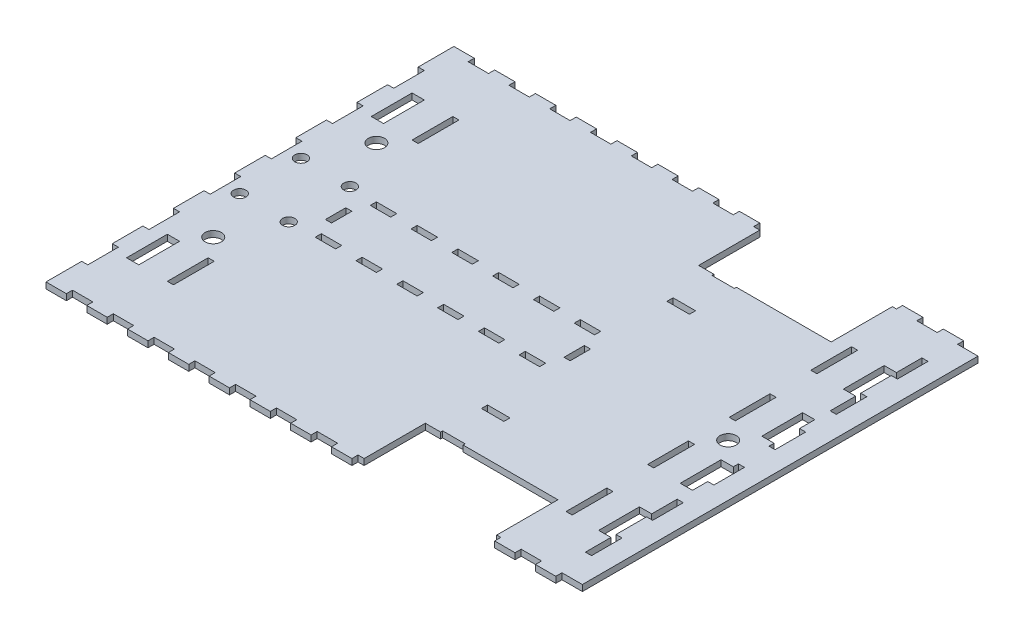
SolidWorks part; units mm, degrees
ref_plane "Front Plane" through (0, 0, 0) normal (0, 0, 1) x (1, 0, 0)
ref_plane "Top Plane" through (0, 0, 0) normal (0, 1, 0) x (1, 0, 0)
ref_plane "Right Plane" through (0, 0, 0) normal (1, 0, 0) x (0, 0, -1)
sketch "Sketch3" plane through (0, 0, 0) normal (0, 1, 0) x (1, 0, 0)
  line L0 (0, 0) -> (-300, 0) construction
  line L1 (-300, -97) -> (-300, 97)
  line L2 (-290, 100) -> (-300, 100)
  line L3 (-290, 97) -> (-290, 100)
  line L4 (-280, 97) -> (-290, 97)
  line L5 (-300, 100) -> (-300, 97)
  line L6 (-270, 100) -> (-280, 100)
  line L7 (-270, 97) -> (-270, 100)
  line L8 (-260, 97) -> (-270, 97)
  line L9 (-280, 100) -> (-280, 97)
  line L10 (-250, 100) -> (-260, 100)
  line L11 (-250, 97) -> (-250, 100)
  line L12 (-240, 97) -> (-250, 97)
  line L13 (-260, 100) -> (-260, 97)
  line L14 (-150, -100) -> (-150, 100) construction
  line L15 (-230, 100) -> (-240, 100)
  line L16 (-230, 97) -> (-230, 100)
  line L17 (-220, 97) -> (-230, 97)
  line L18 (-240, 100) -> (-240, 97)
  line L19 (-210, 100) -> (-220, 100)
  line L20 (-210, 97) -> (-210, 100)
  line L21 (-200, 97) -> (-210, 97)
  line L22 (-40, 97) -> (-40, -97)
  line L23 (-50, 37.5) -> (-53, 37.5)
  line L24 (-50, 7.5) -> (-53, 7.5)
  line L25 (-50, -45.947) -> (-50, 45.947) construction
  line L26 (-247, 37.5) -> (-250, 37.5) construction
  line L27 (-247, 7.5) -> (-250, 7.5) construction
  line L28 (-247, 48.5) -> (-247, -48.5) construction
  line L29 (-247, 48.5) -> (-223, 48.5) construction
  line L30 (-223, 48.5) -> (-223, -48.5) construction
  line L31 (-210, 15) -> (-90, 15) construction
  line L32 (-90, 15) -> (-90, 5) construction
  line L33 (-50, 7.5) -> (-50, 22.5)
  line L34 (-220, 100) -> (-220, 97)
  line L35 (-190, 100) -> (-200, 100)
  line L36 (-190, 97) -> (-190, 100)
  line L37 (-180, 97) -> (-190, 97)
  line L38 (-200, 100) -> (-200, 97)
  line L39 (-170, 100) -> (-180, 100)
  line L40 (-170, 97) -> (-170, 100)
  line L41 (-160, 97) -> (-170, 97)
  line L42 (-180, 100) -> (-180, 97)
  line L43 (-150, 100) -> (-160, 100)
  line L44 (-150, 97) -> (-150, 100)
  line L45 (-140, 97) -> (-150, 97)
  line L46 (-160, 100) -> (-160, 97)
  line L47 (-130, 100) -> (-140, 100)
  line L48 (-130, 97) -> (-130, 100)
  line L49 (-120, 97) -> (-130, 97)
  line L50 (-140, 100) -> (-140, 97)
  line L51 (-110, 100) -> (-120, 100)
  line L52 (-110, 97) -> (-110, 100)
  line L53 (-100, 97) -> (-110, 97)
  line L54 (-120, 100) -> (-120, 97)
  line L55 (-90, 100) -> (-100, 100)
  line L56 (-90, 97) -> (-90, 100)
  line L57 (-80, 97) -> (-90, 97)
  line L58 (-100, 100) -> (-100, 97)
  line L59 (-70, 100) -> (-80, 100)
  line L60 (-70, 97) -> (-70, 100)
  line L61 (-60, 97) -> (-70, 97)
  line L62 (-80, 100) -> (-80, 97)
  line L63 (-50, 100) -> (-60, 100)
  line L64 (-50, 97) -> (-50, 100)
  line L65 (-40, 97) -> (-50, 97)
  line L66 (-60, 100) -> (-60, 97)
  line L67 (-50, 22.5) -> (-53, 22.5)
  line L68 (-210, -15) -> (-90, -15) construction
  line L69 (-53, 7.5) -> (-53, 22.5)
  line L70 (-50, 37.5) -> (-50, 52.5)
  line L71 (-50, 52.5) -> (-53, 52.5)
  line L72 (-53, 37.5) -> (-53, 52.5)
  line L73 (-50, 67.5) -> (-53, 67.5)
  line L74 (-50, 67.5) -> (-50, 82.5)
  line L75 (-50, 82.5) -> (-53, 82.5)
  line L76 (-60, -100) -> (-60, -97)
  line L77 (-40, -97) -> (-50, -97)
  line L78 (-50, -97) -> (-50, -100)
  line L79 (-50, -100) -> (-60, -100)
  line L80 (-80, -100) -> (-80, -97)
  line L81 (-60, -97) -> (-70, -97)
  line L82 (-70, -97) -> (-70, -100)
  line L83 (-70, -100) -> (-80, -100)
  line L84 (-100, -100) -> (-100, -97)
  line L85 (-80, -97) -> (-90, -97)
  line L86 (-90, -97) -> (-90, -100)
  line L87 (-90, -100) -> (-100, -100)
  line L88 (-120, -100) -> (-120, -97)
  line L89 (-100, -97) -> (-110, -97)
  line L90 (-110, -97) -> (-110, -100)
  line L91 (-110, -100) -> (-120, -100)
  line L92 (-140, -100) -> (-140, -97)
  line L93 (-120, -97) -> (-130, -97)
  line L94 (-130, -97) -> (-130, -100)
  line L95 (-130, -100) -> (-140, -100)
  line L96 (-160, -100) -> (-160, -97)
  line L97 (-140, -97) -> (-150, -97)
  line L98 (-150, -97) -> (-150, -100)
  line L99 (-150, -100) -> (-160, -100)
  line L100 (-180, -100) -> (-180, -97)
  line L101 (-160, -97) -> (-170, -97)
  line L102 (-170, -97) -> (-170, -100)
  line L103 (-170, -100) -> (-180, -100)
  line L104 (-200, -100) -> (-200, -97)
  line L105 (-180, -97) -> (-190, -97)
  line L106 (-190, -97) -> (-190, -100)
  line L107 (-190, -100) -> (-200, -100)
  line L108 (-247, -48.5) -> (-223, -48.5) construction
  line L109 (-247, 7.5) -> (-247, 22.5) construction
  line L110 (-220, -100) -> (-220, -97)
  line L111 (-53, 67.5) -> (-53, 82.5)
  line L112 (-53, -67.5) -> (-53, -82.5)
  line L113 (-50, -82.5) -> (-53, -82.5)
  line L114 (-200, -97) -> (-210, -97)
  line L115 (-210, -97) -> (-210, -100)
  line L116 (-210, -100) -> (-220, -100)
  line L117 (-240, -100) -> (-240, -97)
  line L118 (-220, -97) -> (-230, -97)
  line L119 (-230, -97) -> (-230, -100)
  line L120 (-230, -100) -> (-240, -100)
  line L121 (-50, -67.5) -> (-50, -82.5)
  line L122 (-260, -100) -> (-260, -97)
  line L123 (-240, -97) -> (-250, -97)
  line L124 (-250, -97) -> (-250, -100)
  line L125 (-250, -100) -> (-260, -100)
  line L126 (-280, -100) -> (-280, -97)
  line L127 (-260, -97) -> (-270, -97)
  line L128 (-270, -97) -> (-270, -100)
  line L129 (-270, -100) -> (-280, -100)
  line L130 (-300, -100) -> (-300, -97)
  line L131 (-210, 15) -> (-210, -15) construction
  line L132 (-253, -15) -> (-243, -15)
  line L133 (-233, -15) -> (-223, -15)
  line L188 (-247, 22.5) -> (-250, 22.5) construction
  line L189 (-250, 7.5) -> (-250, 22.5) construction
  line L190 (-247, 37.5) -> (-247, 52.5) construction
  line L191 (-247, 52.5) -> (-250, 52.5) construction
  line L192 (-250, 37.5) -> (-250, 52.5) construction
  line L193 (-247, 67.5) -> (-250, 67.5) construction
  line L194 (-247, 67.5) -> (-247, 82.5) construction
  line L195 (-247, 82.5) -> (-250, 82.5) construction
  line L196 (-250, 67.5) -> (-250, 82.5) construction
  line L197 (-250, -67.5) -> (-250, -82.5) construction
  line L198 (-247, -82.5) -> (-250, -82.5) construction
  line L199 (-247, -67.5) -> (-247, -82.5) construction
  line L200 (-247, -67.5) -> (-250, -67.5) construction
  line L201 (-250, -37.5) -> (-250, -52.5) construction
  line L202 (-247, -52.5) -> (-250, -52.5) construction
  line L203 (-247, -37.5) -> (-247, -52.5) construction
  line L204 (-250, -7.5) -> (-250, -22.5) construction
  line L205 (-247, -22.5) -> (-250, -22.5) construction
  line L206 (-247, -7.5) -> (-247, -22.5) construction
  line L207 (-247, -7.5) -> (-250, -7.5) construction
  line L208 (-247, -37.5) -> (-250, -37.5) construction
  line L209 (-50, -67.5) -> (-53, -67.5)
  line L210 (-53, -37.5) -> (-53, -52.5)
  line L211 (-50, -52.5) -> (-53, -52.5)
  line L212 (-50, -37.5) -> (-50, -52.5)
  line L213 (-53, -7.5) -> (-53, -22.5)
  line L214 (-50, -22.5) -> (-53, -22.5)
  line L215 (-50, -7.5) -> (-50, -22.5)
  line L216 (-50, -7.5) -> (-53, -7.5)
  line L217 (-50, -37.5) -> (-53, -37.5)
  line L218 (-210, 0) -> (-258, 0)
  line L219 (-258, -5) -> (-255, -5)
  line L220 (-163, 15) -> (-173, 15)
  line L221 (-243, -12) -> (-243, -15)
  line L222 (-143, 15) -> (-143, 12)
  line L223 (-173, -15) -> (-173, -12)
  line L224 (-163, -15) -> (-173, -15)
  line L225 (-183, 12) -> (-183, 15)
  line L226 (-153, 15) -> (-153, 12)
  line L227 (-163, -12) -> (-163, -15)
  line L228 (-243, -12) -> (-253, -12)
  line L229 (-193, -15) -> (-193, -12)
  line L230 (-258, 5) -> (-255, 5)
  line L231 (-280, -97) -> (-290, -97)
  line L232 (-290, -97) -> (-290, -100)
  line L233 (-290, -100) -> (-300, -100)
  line L234 (-143, 15) -> (-153, 15)
  line L235 (-203, -12) -> (-213, -12)
  line L236 (-213, -15) -> (-213, -12)
  line L237 (-233, -15) -> (-233, -12)
  line L238 (-138, 5) -> (-141, 5)
  line L239 (-243, 12) -> (-243, 15)
  line L240 (-223, 12) -> (-223, 15)
  line L241 (-203, 12) -> (-213, 12)
  line L242 (-153, -15) -> (-153, -12)
  line L243 (-253, 15) -> (-253, 12)
  line L244 (-163, 12) -> (-163, 15)
  line L245 (-141, 5) -> (-141, -5)
  line L246 (-143, -15) -> (-143, -12)
  line L247 (-223, -12) -> (-233, -12)
  line L248 (-258, 15) -> (-258, -15) construction
  line L249 (-233, 15) -> (-233, 12)
  line L250 (-223, 15) -> (-233, 15)
  line L251 (-138, -5) -> (-141, -5)
  line L252 (-183, -15) -> (-193, -15)
  line L253 (-203, 15) -> (-213, 15)
  line L254 (-138, 5) -> (-138, -5)
  line L255 (-258, -15) -> (-138, -15) construction
  line L256 (-255, 5) -> (-255, -5)
  line L257 (-258, 5) -> (-258, -5)
  line L258 (-258, 15) -> (-138, 15) construction
  line L259 (-193, 15) -> (-193, 12)
  line L260 (-163, 12) -> (-173, 12)
  line L261 (-203, -15) -> (-213, -15)
  line L262 (-243, 12) -> (-253, 12)
  line L263 (-183, 15) -> (-193, 15)
  line L264 (-143, 12) -> (-153, 12)
  line L265 (-243, 15) -> (-253, 15)
  line L266 (-213, 15) -> (-213, 12)
  line L267 (-173, 15) -> (-173, 12)
  line L268 (-223, -12) -> (-223, -15)
  line L269 (-143, -12) -> (-153, -12)
  line L270 (-143, -15) -> (-153, -15)
  line L271 (-183, -12) -> (-193, -12)
  line L272 (-203, -12) -> (-203, -15)
  line L273 (-203, 12) -> (-203, 15)
  line L274 (-183, -12) -> (-183, -15)
  line L275 (-253, -15) -> (-253, -12)
  line L276 (-223, 12) -> (-233, 12)
  line L277 (-183, 12) -> (-193, 12)
  line L278 (-163, -12) -> (-173, -12)
  circle A0 centre (-290, 15) radius 3
  circle A1 centre (-266, 15) radius 3
  circle A2 centre (-266, -15) radius 3
  circle A3 centre (-290, -15) radius 3
  point P31 (-250, 36)
  point P80 (-91.5, 0)
  point P82 (-150, 0)
  point P126 (-223, 0)
  point P128 (-250, 18)
  point P129 (-50, 0)
  point P150 (-150, -15)
  point P151 (-150, 15)
  point P183 (-208.5, 0)
  point P212 (-223, 18)
  point P218 (-223, 36)
  point P235 (-198, -15)
  point P236 (-198, 15)
  dimension "D17" = 6
  dimension "D18" = 6
  dimension "D1" = 300
  dimension "D4" = 7.5
  dimension "D5" = 100
  dimension "D6" = 97
  dimension "D7" = 15
  dimension "D8" = 97
  dimension "D9" = 3
  dimension "D10" = 3
  dimension "D11" = 48.5
  dimension "D12" = 24
  dimension "D13" = 60
  dimension "D14" = 15
  dimension "D15" = 24
  dimension "D16" = 15
  dimension "D19" = 194
  dimension "D20" = 10
  dimension "D21" = 3
  dimension "D22" = 7.5
  dimension "D23" = 15
  dimension "D24" = 3
  dimension "D25" = 3
  dimension "D26" = 48
  dimension "D31" = 10
  dimension "D36" = 3
extrude "Boss-Extrude1" add sketch "Sketch3" along normal blind 3 contours L1 L116 L115 L107 L106 L83 L82 L79 L95 L98 L99 L91 L90 L86 region at (-170.2364, 0, 0)
sketch "Sketch5" plane through (0, 3, 0) normal (0, 1, 0) x (1, 0, 0)
  line L0 (-82, 0) -> (-82, 67) construction
  line L2 (-82, 67) -> (-128.5, 67)
  line L3 (-82, 67) -> (-82, 97)
  line L4 (-82, 97) -> (-147, 97)
  line L5 (-147, 67) -> (-147, 97)
  line L7 (-110, 100) -> (-120, 100) construction
  line L8 (-82, 0) -> (-300, 0) construction
  line L9 (-300, 100) -> (-300, -100) construction
  line L10 (-147, -67) -> (-147, -97)
  line L11 (-82, -97) -> (-147, -97)
  line L12 (-82, -67) -> (-82, -97)
  line L13 (-82, -67) -> (-128.5, -67)
  line L14 (-114.5, -67) -> (-114.5, -47) construction
  line L15 (-114.5, -47) -> (-128.5, -47) construction
  line L16 (-128.5, -47) -> (-128.5, -44)
  line L17 (-128.5, -44) -> (-139.5, -44)
  line L18 (-139.5, -44) -> (-139.5, -47)
  line L19 (-139.5, -47) -> (-128.5, -47)
  line L20 (-128.5, -67) -> (-128.5, -66)
  line L21 (-128.5, -66) -> (-139.5, -66)
  line L22 (-139.5, -66) -> (-139.5, -67)
  line L23 (-139.5, -67) -> (-147, -67)
  line L24 (-114.5, 47) -> (-128.5, 47) construction
  line L25 (-114.5, 67) -> (-114.5, 47) construction
  line L26 (-139.5, 66) -> (-139.5, 67)
  line L27 (-128.5, 66) -> (-139.5, 66)
  line L28 (-128.5, 67) -> (-128.5, 66)
  line L29 (-139.5, 47) -> (-128.5, 47)
  line L30 (-139.5, 44) -> (-139.5, 47)
  line L31 (-128.5, 44) -> (-139.5, 44)
  line L32 (-128.5, 47) -> (-128.5, 44)
  line L33 (-139.5, 67) -> (-147, 67)
  dimension "D2" = 30
  dimension "D3" = 3
  dimension "D5" = 14
  dimension "D6" = 3
  dimension "D7" = 11
  dimension "D8" = 20
  dimension "D9" = 1
extrude "Cut-Extrude2" cut sketch "Sketch5" against normal blind 10 contours L5 L2 L3 L4 | L12 L13 L10 L11 | L31 L30 L29 L32 | L17 L18 L19 L16 region at (-114.6094, 3, -81.9131) region at (-114.6094, 3, 81.9131) body kept at (-300, 0, -100)
sketch "Croquis1" plane through (0, 3, 0) normal (0, 1, 0) x (1, 0, 0)
  line L0 (-300, -67.5) -> (-300, -82.5)
  line L25 (-300, 100) -> (-300, -100) construction
  line L26 (-300, 37.5) -> (-300, 52.5)
  line L27 (-297, 37.5) -> (-300, 37.5)
  line L28 (-297, 7.5) -> (-300, 7.5)
  line L29 (-300, -7.5) -> (-297, -7.5)
  line L30 (-297, -22.5) -> (-300, -22.5)
  line L31 (-297, -7.5) -> (-297, -22.5)
  line L32 (-297, 82.5) -> (-297, 67.5)
  line L33 (-300, -22.5) -> (-300, -7.5)
  line L34 (-297, -37.5) -> (-297, -52.5)
  line L35 (-297, 67.5) -> (-300, 67.5)
  line L36 (-300, 67.5) -> (-300, 82.5)
  line L37 (-297, 52.5) -> (-297, 37.5)
  line L38 (-300, 22.5) -> (-297, 22.5)
  line L39 (-300, -37.5) -> (-297, -37.5)
  line L40 (-297, -52.5) -> (-300, -52.5)
  line L41 (-300, 52.5) -> (-297, 52.5)
  line L42 (-300, -52.5) -> (-300, -37.5)
  line L43 (-300, 82.5) -> (-297, 82.5)
  line L44 (-297, 22.5) -> (-297, 7.5)
  line L45 (-300, 7.5) -> (-300, 22.5)
  line L46 (-300, -67.5) -> (-297, -67.5)
  line L47 (-297, -67.5) -> (-297, -82.5)
  line L48 (-297, -82.5) -> (-300, -82.5)
  dimension "D1" = 15
  dimension "D2" = 15
extrude "Cortar-Extruir1" cut sketch "Croquis1" against normal blind 10
sketch "Croquis2" plane through (0, 3, 0) normal (0, 1, 0) x (1, 0, 0)
  line L0 (-40, 0) -> (-53, 0) construction
  line L1 (-40, 97) -> (-40, -97) construction
  line L2 (-53, 10) -> (-53, -10) construction
  line L3 (-53, -7.5) -> (-53, -22.5) construction
  line L4 (-53, -10) -> (-59, -10)
  line L5 (-59, -10) -> (-59, -30)
  line L6 (-59, -30) -> (-53, -30)
  line L7 (-53, -30) -> (-53, -10)
  line L8 (-53, -30) -> (-53, -50) construction
  line L9 (-53, -37.5) -> (-53, -52.5) construction
  line L10 (-53, -50) -> (-59, -50)
  line L11 (-59, -50) -> (-59, -70)
  line L12 (-59, -70) -> (-53, -70)
  line L13 (-53, -67.5) -> (-53, -82.5) construction
  line L14 (-53, -70) -> (-53, -50)
  line L15 (-53, 30) -> (-53, 50) construction
  line L16 (-53, 70) -> (-53, 50)
  line L17 (-59, 70) -> (-53, 70)
  line L18 (-59, 50) -> (-59, 70)
  line L19 (-53, 50) -> (-59, 50)
  line L20 (-53, 30) -> (-53, 10)
  line L21 (-59, 30) -> (-53, 30)
  line L22 (-59, 10) -> (-59, 30)
  line L23 (-53, 10) -> (-59, 10)
  line L24 (-59, 70) -> (-72, 70) construction
  line L25 (-72, 70) -> (-75, 70)
  line L26 (-72, 70) -> (-72, 50)
  line L27 (-72, 50) -> (-75, 50)
  line L28 (-75, 50) -> (-75, 70)
  line L29 (-72, 30) -> (-75, 30)
  line L30 (-75, 30) -> (-75, 10)
  line L31 (-75, 10) -> (-72, 10)
  line L32 (-72, 10) -> (-72, 30)
  line L33 (-72, -10) -> (-75, -10)
  line L34 (-75, -10) -> (-75, -30)
  line L35 (-75, -30) -> (-72, -30)
  line L36 (-72, -30) -> (-72, -10)
  line L37 (-72, -50) -> (-75, -50)
  line L38 (-75, -50) -> (-75, -70)
  line L39 (-75, -70) -> (-72, -70)
  line L40 (-72, -70) -> (-72, -50)
  line L45 (-290.5, 30) -> (-290.5, 50) construction
  line L46 (-290.5, -30) -> (-290.5, -50) construction
  line L49 (-270.5, -70) -> (-270.5, -50)
  line L50 (-267.5, -70) -> (-270.5, -70)
  line L51 (-267.5, -50) -> (-267.5, -70)
  line L52 (-270.5, -50) -> (-267.5, -50)
  line L61 (-267.5, 50) -> (-267.5, 70)
  line L62 (-270.5, 50) -> (-267.5, 50)
  line L63 (-270.5, 70) -> (-270.5, 50)
  line L64 (-270.5, 70) -> (-267.5, 70)
  line L69 (-290.5, 50) -> (-284.5, 50)
  line L70 (-284.5, 50) -> (-284.5, 70)
  line L71 (-284.5, 70) -> (-290.5, 70)
  line L72 (-290.5, 70) -> (-290.5, 50)
  line L73 (-290.5, -70) -> (-290.5, -50)
  line L74 (-284.5, -70) -> (-290.5, -70)
  line L75 (-284.5, -50) -> (-284.5, -70)
  line L76 (-290.5, -50) -> (-284.5, -50)
  circle A0 centre (-65.5, 0) radius 4
  circle A3 centre (-278, -40) radius 4
  circle A4 centre (-278, 40) radius 4
  dimension "D8" = 8
  dimension "D11" = 8
  dimension "D12" = 8
  dimension "D1" = 10
  dimension "D2" = 6
  dimension "D3" = 20
  dimension "D4" = 20
  dimension "D5" = 13
  dimension "D6" = 3
  dimension "D7" = 20
  dimension "D9" = 14
extrude "Cortar-Extruir2" cut sketch "Croquis2" against normal blind 10
